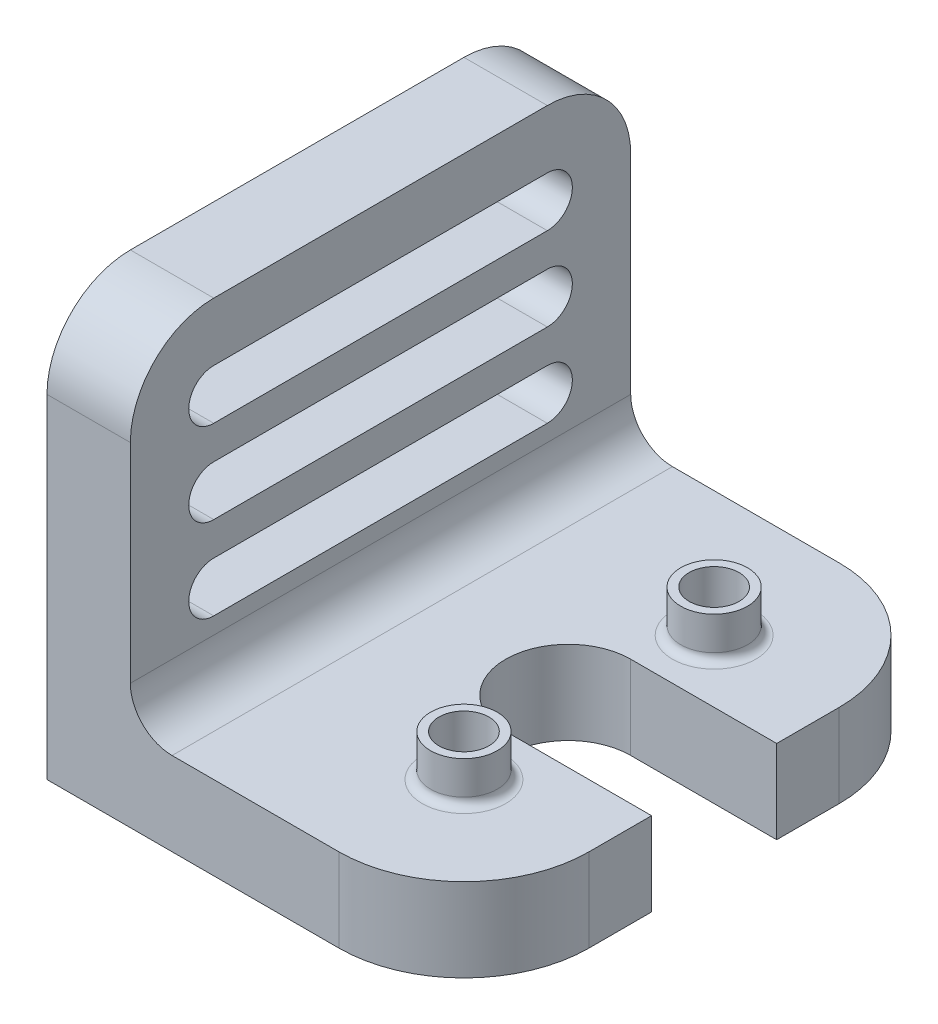
SolidWorks part; units mm, degrees
note: The reader was unsure of these and kept them because the rebuilt part matched: shared geometry of "Sketch3<3>".
ref_plane "Front Plane" through (0, 0, 0) normal (0, 0, 1) x (1, 0, 0)
ref_plane "Top Plane" through (0, 0, 0) normal (0, 1, 0) x (1, 0, 0)
ref_plane "Right Plane" through (0, 0, 0) normal (1, 0, 0) x (0, 0, -1)
sketch "Sketch1" plane through (0, 0, 0) normal (0, 0, 1) x (1, 0, 0)
  line L0 (0, 0) -> (100, 0)
  line L1 (100, 0) -> (100, 20)
  line L2 (100, 20) -> (20, 20)
  line L3 (20, 20) -> (20, 100)
  line L4 (20, 100) -> (0, 100)
  line L5 (0, 100) -> (0, 0)
  dimension "D1" = 100
  dimension "D2" = 100
  dimension "D3" = 20
  dimension "D4" = 20
extrude "Boss-Extrude1" add sketch "Sketch1" along normal mid plane 120
fillet "Fillet1" radius 20 2 edges at (10, 100, -60) (10, 100, 60)
fillet "Fillet2" radius 30 2 edges at (100, 10, -60) (100, 10, 60)
fillet "Fillet3" radius 10 1 edges at (20, 20, 0)
sketch "Sketch2" plane through (20, 0, 0) normal (1, 0, 0) x (0, 0, -1)
  line L0 (-40, 80) -> (40, 80) construction
  line L1 (-40, 86) -> (40, 86)
  line L2 (-40, 74) -> (40, 74)
  line L3 (-40, 60) -> (40, 60) construction
  line L4 (-40, 66) -> (40, 66)
  line L5 (-40, 54) -> (40, 54)
  line L6 (-40, 40) -> (40, 40) construction
  line L7 (-40, 46) -> (40, 46)
  line L8 (-40, 34) -> (40, 34)
  line L9 (-40, 100) -> (40, 100) construction
  line L11 (-60, 30) -> (-60, 80) construction
  arc A0 (-40, 86) -> (-40, 74) centre (-40, 80) ccw
  arc A1 (40, 74) -> (40, 86) centre (40, 80) ccw
  arc A2 (-40, 66) -> (-40, 54) centre (-40, 60) ccw
  arc A3 (40, 54) -> (40, 66) centre (40, 60) ccw
  arc A4 (-40, 46) -> (-40, 34) centre (-40, 40) ccw
  arc A5 (40, 34) -> (40, 46) centre (40, 40) ccw
  point P2 (0, 80)
  point P7 (0, 60)
  point P14 (0, 40)
  dimension "D1" = 6
  dimension "D2" = 20
  dimension "D3" = 20
  dimension "D4" = 20
  dimension "D5" = 80
  dimension "D6" = 20
extrude "Cut-Extrude1" cut sketch "Sketch2" against normal up to next
sketch "Sketch3" plane through (0, 20, 0) normal (0, 1, 0) x (1, 0, 0)
  line L0 (100, 0) -> (65, 0) construction
  line L1 (100, -30) -> (100, 30) construction
  line L2 (100, -15) -> (65, -15)
  line L3 (100, 15) -> (65, 15)
  line L4 (100, -15) -> (100, 15)
  line L5 (70, -60) -> (30, -60) construction
  line L6 (70, 60) -> (30, 60) construction
  arc A1 (65, 15) -> (65, -15) centre (65, 0) ccw
  circle A2 centre (70, 30) radius 6
  circle A3 centre (70, 30) radius 8
  circle A4 centre (70, -30) radius 6
  circle A5 centre (70, -30) radius 8
  point P4 (87.1205, -2.5926)
  point P17 (0, 0)
  dimension "D2" = 15
  dimension "D6" = 12
  dimension "D7" = 16
  dimension "D1" = 35
  dimension "D3" = 60
  dimension "D4" = 45
  dimension "D5" = 30
  dimension "D8" = 30
  dimension "D9" = 30
  dimension "D10" = 30
extrude "Cut-Extrude2" cut sketch "Sketch3" against normal up to next
extrude "Boss-Extrude2" add sketch "Sketch3<3>" along normal blind 10 contours A5 A4 | A3 A2
sketch "Sketch3<3>" plane through (0, 20, 0) normal (0, 1, 0) x (1, 0, 0) same geometry as "Sketch3"
fillet "Fillet4" radius 2 2 edges at (78, 20, 30) (78, 20, -30)
